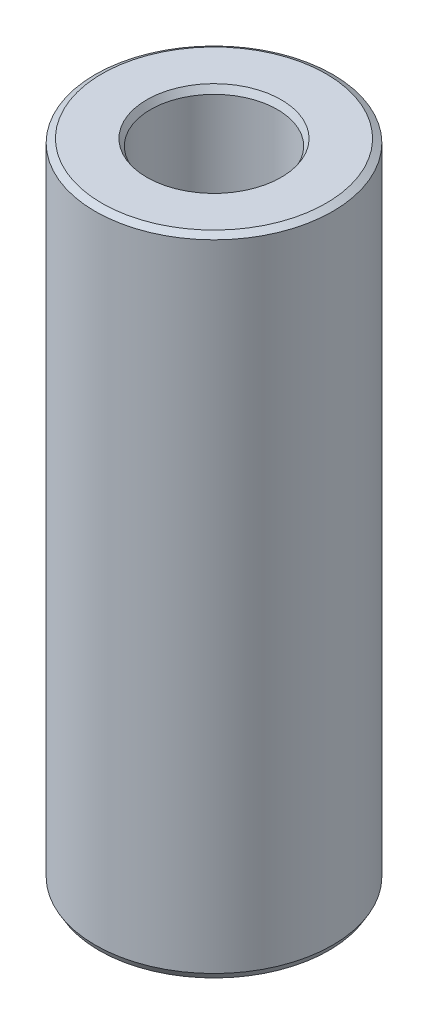
SolidWorks part; units mm, degrees
ref_plane "Front Plane" through (0, 0, 0) normal (0, 0, 1) x (1, 0, 0)
ref_plane "Top Plane" through (0, 0, 0) normal (0, 1, 0) x (1, 0, 0)
ref_plane "Right Plane" through (0, 0, 0) normal (1, 0, 0) x (0, 0, -1)
sketch "Sketch1" plane through (0, 0, 0) normal (0, 1, 0) x (1, 0, 0)
  circle A0 centre (0, 0) radius 57.5
  dimension "SLEEVE_OD" = 115
extrude "Boss-Extrude1" add sketch "Sketch1" along normal blind 312.7891
sketch "Sketch2" plane through (0, 0, 0) normal (0, 1, 0) x (1, 0, 0)
  circle A0 centre (0, 0) radius 30.7275
  dimension "BORE_D" = 61.4549
extrude "Cut-Extrude1" cut sketch "Sketch2" along normal through all
chamfer "Chamfer1" distance 1.8452 angle 59.876 4 edges at (0, 312.7891, 30.7275) (0, 0, 30.7275) (0, 0, 57.5) (0, 312.7891, 57.5) first distance on face at (0, 312.7891, 30.7275) first distance on face at (0, 0, 30.7275) first distance on face at (0, 312.7891, 57.5)
